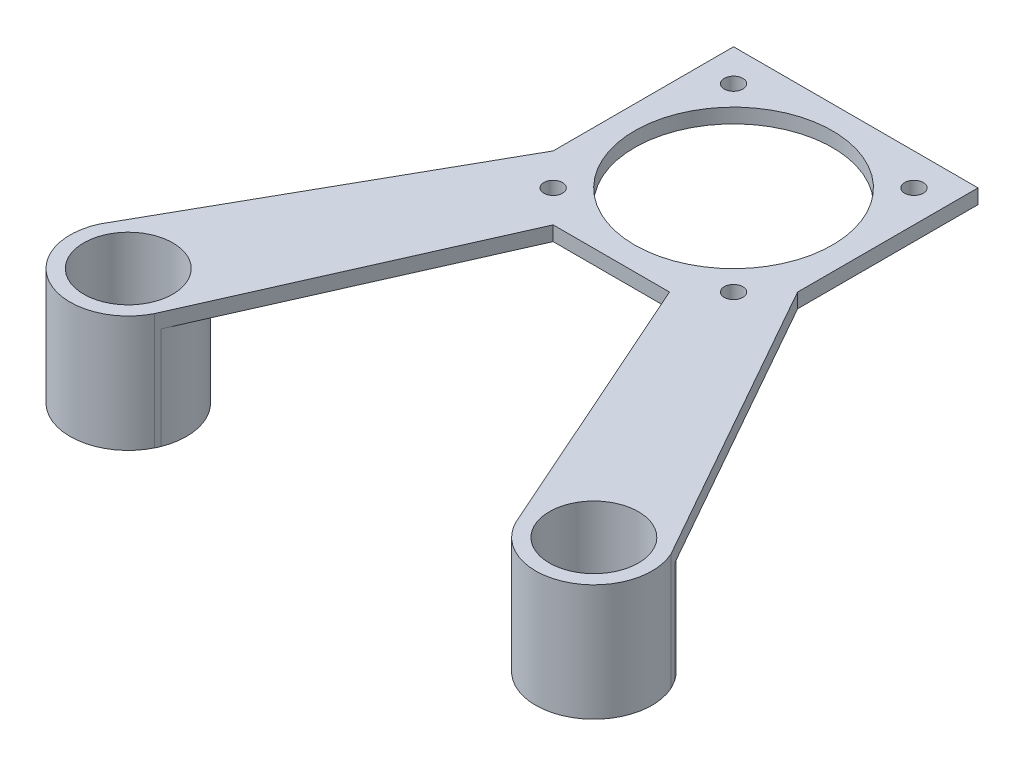
SolidWorks part; units mm, degrees
ref_plane "前视基准面" through (0, 0, 0) normal (0, 0, 1) x (1, 0, 0)
ref_plane "上视基准面" through (0, 0, 0) normal (0, 1, 0) x (1, 0, 0)
ref_plane "右视基准面" through (0, 0, 0) normal (1, 0, 0) x (0, 0, -1)
sketch "草图6" plane through (0, 0, 0) normal (0, 1, 0) x (1, 0, 0)
  line L1 (-21, -21) -> (21, -21)
  line L2 (-21, -21) -> (-21, 21)
  line L3 (-21, 21) -> (21, 21)
  line L4 (21, -21) -> (21, 21)
  line L5 (0, 21) -> (0, -21) construction
  line L6 (-21, 0) -> (21, 0) construction
  circle A0 centre (15.5, 15.5) radius 1.6
  circle A1 centre (-15.5, 15.5) radius 1.6
  circle A2 centre (-15.5, -15.5) radius 1.6
  circle A3 centre (15.5, -15.5) radius 1.6
  circle A4 centre (0, 0) radius 17
  point P0 (0, 0)
extrude "凸台-拉伸1" add sketch "草图6" along normal blind 2.5
sketch "草图7" plane through (0, 2.5, 0) normal (0, 1, 0) x (1, 0, 0)
  line L2 (21, -10) -> (49.0892, -59.8303)
  line L4 (-10, -21) -> (-31.0355, -68.4315)
  line L5 (-21, -10) -> (-49.0892, -59.8303)
  line L6 (10, -21) -> (31.0355, -68.4315)
  circle A0 centre (-40, -64) radius 10
  circle A1 centre (40, -64) radius 10
  circle A2 centre (-40, -64) radius 7.65
  circle A3 centre (40, -64) radius 7.65
  line M9 (21, -21) -> (21, 21)
  line M11 (-21, 21) -> (-21, -21)
  line M12 (-21, -21) -> (21, -21)
extrude "凸台-拉伸5" add sketch "草图7" against normal blind 2.5 contours A1 L2 L6 M9 M12 | A0 L4 L5 M12 M11 | A1 A3 | A0 A2 region at (-27.3301, 2.5, 38.6598) region at (27.3301, 2.5, 38.6598) region at (48.4348, 2.5, 59.2453) region at (-31.1252, 2.5, 67.9359)
extrude "凸台-拉伸7" add sketch "草图7<7>" against normal blind 20 contours A1 A3 region at (48.4348, 2.5, 59.2453)
sketch "草图7<7>" plane through (0, 2.5, 0) normal (0, 1, 0) x (1, 0, 0) same geometry as "草图7"
extrude "凸台-拉伸8" add sketch "草图7<8>" against normal blind 20 contours A0 A2 region at (-31.1252, 2.5, 67.9359)
sketch "草图7<8>" plane through (0, 2.5, 0) normal (0, 1, 0) x (1, 0, 0) same geometry as "草图7"
